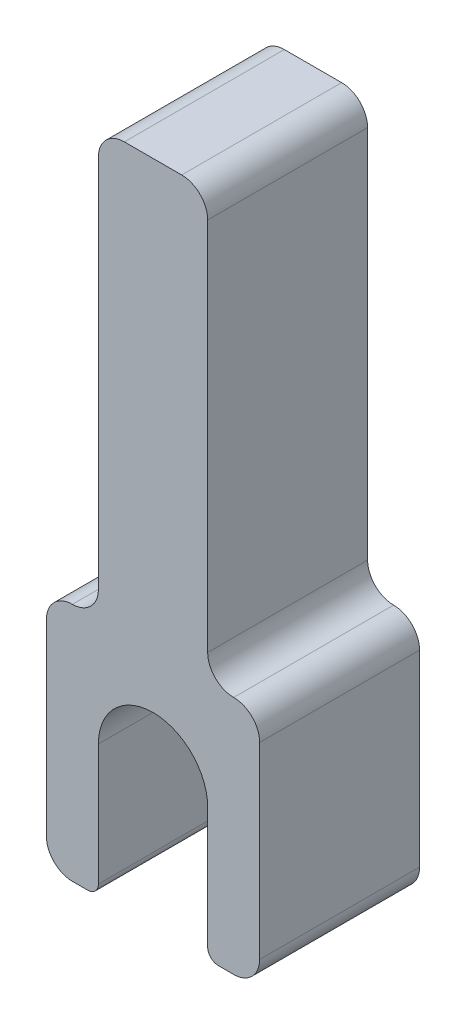
SolidWorks part; units mm, degrees
ref_plane "Front Plane" through (0, 0, 0) normal (0, 0, 1) x (1, 0, 0)
ref_plane "Top Plane" through (0, 0, 0) normal (0, 1, 0) x (1, 0, 0)
ref_plane "Right Plane" through (0, 0, 0) normal (1, 0, 0) x (0, 0, -1)
sketch "Sketch1" plane through (0, 0, 0) normal (0, 0, 1) x (1, 0, 0)
  line L0 (-4, -4.95) -> (-4, 4.05)
  line L2 (4, 4.05) -> (4, -4.95)
  line L3 (4, -4.95) -> (2.05, -4.95)
  line L4 (2.05, -4.95) -> (2.05, 0)
  line L5 (-2.05, 0) -> (-2.05, -4.95)
  line L6 (-2.05, -4.95) -> (-4, -4.95)
  line L7 (-4, 4.05) -> (-2.05, 4.05)
  line L8 (-2.05, 4.05) -> (-2.05, 20.05)
  line L9 (-2.05, 20.05) -> (2.05, 20.05)
  line L10 (2.05, 20.05) -> (2.05, 4.05)
  line L11 (2.05, 4.05) -> (4, 4.05)
  arc A0 (2.05, 0) -> (-2.05, 0) centre (0, 0) ccw
  dimension "D1" = 2.05
  dimension "D3" = 7
  dimension "D2" = 8
  dimension "D4" = 25
  dimension "D5" = 9
extrude "Boss-Extrude1" add sketch "Sketch1" along normal blind 6
fillet "Fillet1" radius 0.975 8 edges at (-4, -4.95, 3) (-4, 4.05, 3) (-2.05, 4.05, 3) (4, 4.05, 3) (4, -4.95, 3) (2.05, 4.05, 3) (-2.05, 20.05, 3) (2.05, 20.05, 3)
fillet "Fillet2" radius 0.4 2 edges at (2.05, -4.95, 3) (-2.05, -4.95, 3)
